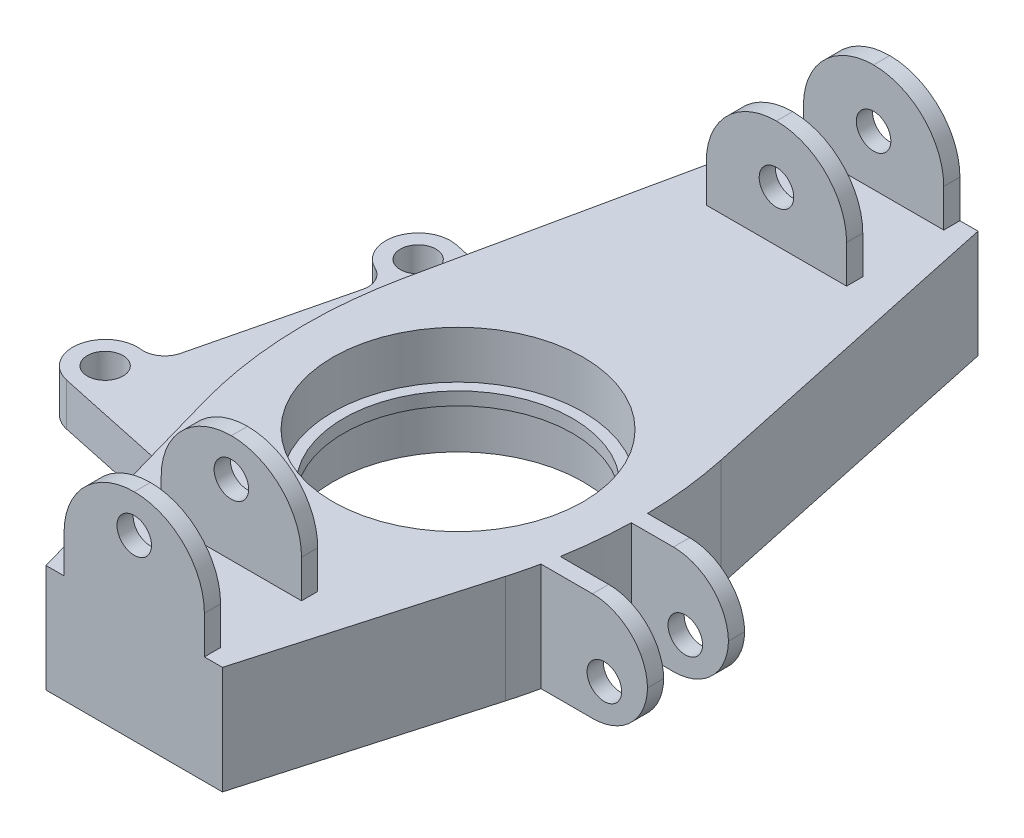
SolidWorks part; units mm, degrees
ref_plane "Front Plane" through (0, 0, 0) normal (0, 0, 1) x (1, 0, 0)
ref_plane "Top Plane" through (0, 0, 0) normal (0, 1, 0) x (1, 0, 0)
ref_plane "Right Plane" through (0, 0, 0) normal (1, 0, 0) x (0, 0, -1)
sketch "Sketch1" plane through (0, 0, 0) normal (0, 1, 0) x (1, 0, 0)
  line L1 (37.1752, 24.7132) -> (20.7644, 101.6)
  line L2 (20.7644, 101.6) -> (-20.7644, 101.6)
  line L4 (20.7644, 101.6) -> (20.7644, -76.2) construction
  line L8 (0, 0) -> (0, 101.6) construction
  line L9 (0, 0) -> (42.4501, 0) construction
  line L10 (35.5332, -24.3048) -> (20.7644, -76.2)
  line L11 (20.7644, -76.2) -> (-20.7644, -76.2)
  line L12 (-37.1752, 24.7132) -> (-20.7644, 101.6)
  line L13 (-35.5332, -24.3048) -> (-20.7644, -76.2)
  line L14 (-20.7644, 101.6) -> (-20.7644, -76.2) construction
  circle A0 centre (0, 0) radius 29.464
  circle A2 centre (0, 0) radius 120.65
  arc A4 (-37.1752, 24.7132) -> (-35.5332, -24.3048) centre (62.1866, 3.5052) ccw
  arc A5 (35.5332, -24.3048) -> (37.1752, 24.7132) centre (-62.1866, 3.5052) ccw
  point P9 (0, -76.2)
  point P10 (0, -29.464)
  point P11 (29.464, 0)
  point P16 (-29.464, 0)
  point P18 (-42.4501, 0)
  dimension "D2" = 58.928
  dimension "D3" = 12.7
  dimension "D4" = 101.6
  dimension "D5" = 177.8
  dimension "D1" = 241.3
  dimension "D6" = 101.6
extrude "Base" add sketch "Sketch1" along normal blind 25.4 contours L12 L13 L11 L10 L1 L2 A0 region at (37.4126, 0, -0.1687)
sketch "Sketch2" plane through (0, 0, 0) normal (0, 1, 0) x (1, 0, 0)
  line L0 (16.51, 101.6) -> (16.51, 97.79)
  line L1 (0, 101.6) -> (0, -76.2) construction
  line L2 (16.51, 97.79) -> (-16.51, 97.79)
  line L3 (-16.51, 97.79) -> (-16.51, 101.6)
  line L4 (20.7644, 101.6) -> (-20.7644, 101.6) construction
  line L5 (-16.51, 101.6) -> (16.51, 101.6)
  line L11 (20.7644, 101.6) -> (-20.7644, 101.6) construction
  line L12 (0, 0) -> (35.6331, 0) construction
  line L13 (-16.51, 78.74) -> (-16.51, 74.93)
  line L14 (-16.51, 74.93) -> (16.51, 74.93)
  line L15 (16.51, 74.93) -> (16.51, 78.74)
  line L16 (16.51, 78.74) -> (-16.51, 78.74)
  line L26 (16.51, -72.39) -> (-16.51, -72.39)
  line L32 (20.7644, -76.2) -> (-20.7644, -76.2) construction
  line L33 (-16.51, -72.39) -> (-16.51, -76.2)
  line L34 (-16.51, -76.2) -> (16.51, -76.2)
  line L35 (16.51, -76.2) -> (16.51, -72.39)
  line L36 (-16.51, -49.53) -> (16.51, -49.53)
  line L37 (16.51, -49.53) -> (16.51, -53.34)
  line L38 (16.51, -53.34) -> (-16.51, -53.34)
  line L39 (-16.51, -53.34) -> (-16.51, -49.53)
  point P4 (0, 101.6)
  point P45 (-16.51, 99.695)
  dimension "D2" = 3.81
  dimension "D3" = 3.81
  dimension "D4" = 19.05
  dimension "D5" = 2
  dimension "D11" = 33.02
extrude "A-Arms" add sketch "Sketch2" against normal blind 25.4
fillet "Fillet a-arm tab f" radius 16.51 8 edges at (16.51, -25.4, -99.695) (-16.51, -25.4, -76.835) (-16.51, -25.4, -99.695) (-16.51, -25.4, 74.295) (16.51, -25.4, 74.295) (-16.51, -25.4, 51.435) (16.51, -25.4, 51.435) (16.51, -25.4, -76.835)
ref_plane "Plane1" through (0, 1, 0) normal (0, -1, 0) x (-1, 0, 0)
sketch "Sketch3" plane through (0, 25.4, 0) normal (0, -1, 0) x (-1, 0, 0)
  line L0 (32.133, 48.3368) -> (53.1736, 52.8277)
  line L2 (34.3293, -28.5351) -> (71.4838, -20.6048)
  line L3 (55.1887, 32.6617) -> (63.5548, -1.731)
  line L5 (37.1752, 24.7132) -> (20.7644, 101.6) construction
  line L8 (35.5332, -24.3048) -> (20.7644, -76.2) construction
  line L9 (35.5332, -24.3048) -> (20.7644, -76.2) construction
  line L10 (37.1752, 24.7132) -> (20.7644, 101.6) construction
  line L11 (35.5332, -24.3048) -> (20.7644, -76.2)
  line L12 (37.1752, 24.7132) -> (20.7644, 101.6)
  circle A0 centre (0, 0) radius 71.12
  circle A1 centre (54.7642, 45.3756) radius 4.191
  circle A2 centre (69.8932, -13.1527) radius 4.191
  arc A3 (57.9805, 38.4677) -> (53.1736, 52.8277) centre (54.7642, 45.3756) ccw
  arc A4 (71.4838, -20.6048) -> (69.0518, -5.5793) centre (69.8932, -13.1527) ccw
  arc A5 (63.5548, -1.731) -> (69.0518, -5.5793) centre (68.4909, -0.5303) ccw
  arc A6 (55.1887, 32.6617) -> (57.9805, 38.4677) centre (60.1248, 33.8624) cw
  arc A7 (35.5332, -24.3048) -> (37.1752, 24.7132) centre (-62.1866, 3.5052) ccw construction
  arc A8 (35.5332, -24.3048) -> (37.1752, 24.7132) centre (-62.1866, 3.5052) ccw
  dimension "D1" = 60.452
  dimension "D2" = 142.24
  dimension "D3" = 8.382
  dimension "D4" = 8.382
  dimension "D5" = 15.24
  dimension "D6" = 15.24
  dimension "D7" = 5.08
extrude "Boss-Extrude3" add sketch "Sketch3" along normal blind 10 contours A6 L3 A5 A4 A0 A2 L2 L0 A1 A3 | A3 A0 A1 L0 | A4 L2 A0 A2 region at (-49.0548, 25.4, -9.0509) region at (-50.9588, 25.4, -52.1564) region at (-68.6224, 25.4, 19.375)
sketch "Sketch6" plane through (0, 0, -101.6) normal (0, 0, -1) x (-1, 0, 0)
  line L0 (0, -25.4) -> (0, 3.0923) construction
  circle A1 centre (0, -11.8937) radius 4.064
  dimension "D1" = 14.986
  dimension "D2" = 8.128
extrude "Tab Holes 1" cut sketch "Sketch6" against normal blind 38.1
sketch "Sketch7" plane through (0, 0, 49.53) normal (0, 0, -1) x (-1, 0, 0)
  line L0 (0, -25.4) -> (0, 0) construction
  circle A0 centre (0, -16.51) radius 4.064
  dimension "D1" = 16.51
  dimension "D2" = 8.128
extrude "Tab Holes 2" cut sketch "Sketch7" against normal through all
ref_plane "midplane" through (0, 12.7, 0) normal (0, 1, 0) x (1, 0, 0)
sketch "Sketch8" plane through (0, 12.7, 0) normal (0, 1, 0) x (1, 0, 0)
  circle A2 centre (0, 0) radius 29.464 construction
  circle A3 centre (0, 0) radius 29.464
  circle A5 centre (0, 0) radius 26.924
  dimension "D1" = 2.54
extrude "mid-feature bearing" add sketch "Sketch8" along normal blind 1.524 and the other way blind 1.524
sketch "pushrod" plane through (0, 0, 0) normal (0, 1, 0) x (1, 0, 0)
  line L1 (-32.844, -79.7284) -> (0.176, -79.7284)
  line L2 (-32.844, -79.7284) -> (-32.844, -75.9184)
  line L3 (-32.844, -75.9184) -> (0.176, -75.9184)
  line L4 (0.176, -79.7284) -> (0.176, -75.9184)
  line L5 (-45.2966, -56.8684) -> (3.0871, -56.8684) construction
  line L6 (0.176, -75.9184) -> (-3.634, -75.9184)
  line L7 (0.176, -75.9184) -> (0.176, -56.8684)
  line L8 (0.176, -56.8684) -> (-3.634, -56.8684)
  line L9 (-3.634, -75.9184) -> (-3.634, -56.8684)
  line L10 (-32.844, -75.9184) -> (-29.034, -75.9184)
  line L11 (-32.844, -75.9184) -> (-32.844, -56.8684)
  line L12 (-32.844, -56.8684) -> (-29.034, -56.8684)
  line L13 (-29.034, -75.9184) -> (-29.034, -56.8684)
  dimension "D1" = 3.81
  dimension "D2" = 3.81
  dimension "D3" = 3.81
  dimension "D4" = 25.4
mirror "Mirror2" [suppressed] of bodies 108
delete or keep bodies "Body-Delete/Keep 1" [suppressed] type delete bodies bodies 108
ref_plane "Plane2" through (0, 0, -88.265) normal (0, 0, -1) x (-1, 0, 0)
ref_axis "Axis1" through (0, -11.8937, -74.93) along (0, 0, -1)
ref_point "top wishbont att pt"
ref_axis "Axis3" through (0, -16.51, 53.34) along (0, 0, -1)
ref_plane "Plane3" through (0, 0, 62.865) normal (0, 0, -1) x (-1, 0, 0)
ref_point "bottom wishbone"
sketch "Sketch10" plane through (0, 0, 0) normal (0, -1, 0) x (1, 0, 0)
  line L1 (37.9191, 13.856) -> (37.1831, 17.666)
  line L2 (39.3912, -1.384) -> (62.2593, -1.384)
  line L3 (62.2593, -1.384) -> (62.2593, -5.194)
  line L4 (62.2593, -5.194) -> (39.3993, -5.194)
  line L5 (62.2593, 13.856) -> (62.2593, 17.666)
  line L6 (62.2593, 17.666) -> (37.1831, 17.666)
  line L8 (37.9191, 13.856) -> (62.2593, 13.856)
  line L9 (35.5332, 24.3048) -> (20.7644, 76.2) construction
  line L10 (35.5332, 24.3048) -> (20.7644, 76.2)
  arc A1 (37.1752, -24.7132) -> (35.5332, 24.3048) centre (-62.1866, -3.5052) ccw construction
  arc A2 (37.1752, -24.7132) -> (35.5332, 24.3048) centre (-62.1866, -3.5052) ccw
  arc A3 (37.1752, -24.7132) -> (35.5332, 24.3048) centre (-62.1866, -3.5052) ccw construction
  arc M33 (37.1752, -24.7132) -> (35.5332, 24.3048) centre (-62.1866, -3.5052) ccw
  dimension "D1" = 19.05
  dimension "D2" = 22.86
  dimension "D3" = 3.81
  dimension "D4" = 3.81
extrude "Boss-Extrude4" add sketch "Sketch10" against normal up to surface (25.4 mm away) contours L8 L5 L6 M33 | L4 L3 L2 M33 region at (49.9106, 0, 15.7704) region at (50.8333, 0, -3.2889) up to face at (-26.6415, 25.4, -12.1227)
fillet "Fillet1" radius 12.954 4 edges at (62.2593, 25.4, 15.761) (62.2593, 25.4, -3.289) (62.2593, 0, 15.761) (62.2593, 0, -3.289)
sketch "Sketch11" plane through (0, 0, -5.194) normal (0, 0, -1) x (-1, 0, 0)
  line L0 (-62.2568, 16.51) -> (-48.6985, 16.51) construction
  line L1 (-62.2568, 12.7) -> (-62.2568, 21.1564) construction
  circle A0 centre (-52.0968, 16.51) radius 4.064
  point P2 (0, 0)
  dimension "D1" = 10.16
  dimension "D2" = 2.54
extrude "Cut-Extrude1" cut sketch "Sketch11" against normal through all contours A0 region at (52.0968, 16.51, -5.194)
ref_axis "rotation axis" through (0, -16.51, 62.865) along (0, 0.0305, -0.9995)
ref_axis "Axis5" through (52.0968, 16.51, -1.384) along (0, 0, -1)
ref_plane "Plane4" through (0, 0, 6.236) normal (0, 0, -1) x (-1, 0, 0)
ref_point "tierod"
mirror "Mirror5" about plane through (0, 0, 0) normal (0, 1, 0) of bodies 120
delete or keep bodies "Body-Delete/Keep 3" type delete bodies bodies 120
ref_axis "Axis6" through (0, 11.8937, -97.79) along (0, 0, -1)
ref_point "top wish 2"
ref_axis "Axis7" through (0, 16.51, 53.34) along (0, 0, -1)
ref_point "bottom wish 2"
ref_axis "rot ax" through (0, 16.51, 62.865) along (0, -0.0305, -0.9995)
ref_axis "Axis9" through (52.0968, -16.51, -1.384) along (0, 0, -1)
ref_point "tie in 2"
mirror "Mirror3" [suppressed] of bodies 111
mirror "Mirror4" [suppressed] of bodies 111
delete or keep bodies "Body-Delete/Keep 2" [suppressed] type delete bodies bodies 111
